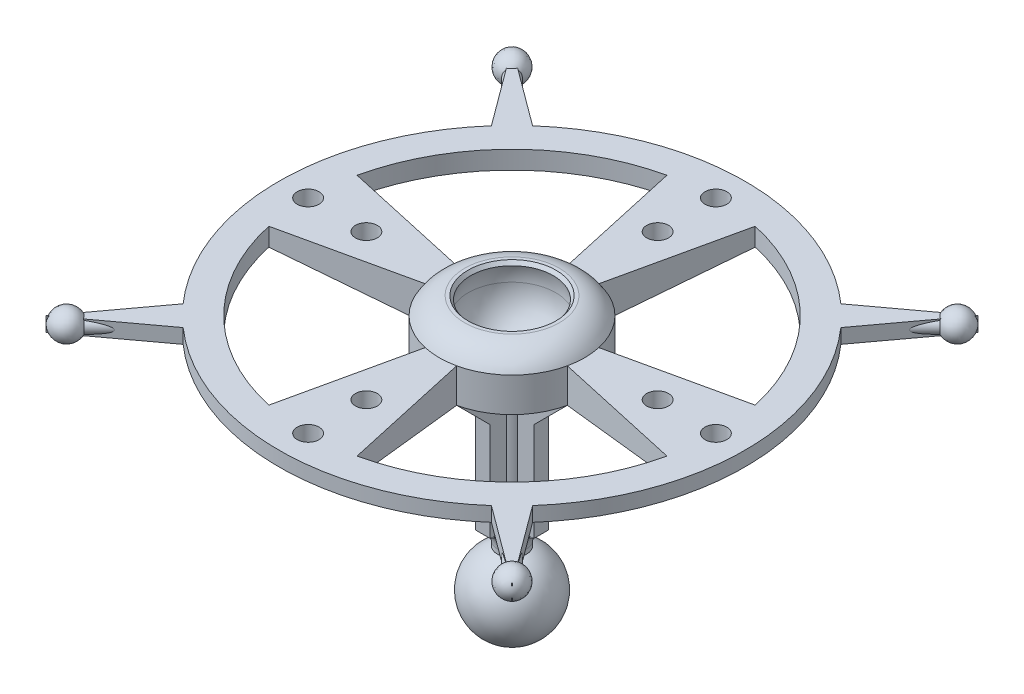
SolidWorks part; units mm, degrees
other "Markup1"
sketch "Sketch8" plane through (-15, -13.5, -15) normal (-0.6433, -0.4106, -0.6463) x (0.1908, 0.7315, -0.6546)
ref_plane "Front Plane" through (0, 0, 0) normal (0, 0, 1) x (1, 0, 0)
ref_plane "Top Plane" through (0, 0, 0) normal (0, 1, 0) x (1, 0, 0)
ref_plane "Right Plane" through (0, 0, 0) normal (1, 0, 0) x (0, 0, -1)
sketch "Sketch1" plane through (0, 0, 0) normal (1, 0, 0) x (0, 0, -1)
  line L0 (0, 4) -> (0, 0) construction
  line L1 (0, 0) -> (0, -9.5)
  line L2 (0, -9.5) -> (0, -12.3) construction
  line L3 (-4, 4) -> (-16, 4)
  line L4 (-16, 4) -> (-16, 3)
  line L5 (-16, 3) -> (-3.048, 1.4097)
  line L6 (-4, 4) -> (-3, 4)
  line L7 (0, 0.127) -> (-1, 0.127) construction
  line L8 (1, 0.127) -> (1, -9.6847) construction
  line L9 (0, -9.6847) -> (-1, -9.6847) construction
  line L10 (-1, 0.127) -> (-1, -9.6847)
  line L11 (0, -15.1) -> (0, -9.5)
  line L12 (0, 1) -> (0, 0)
  line L13 (1, 0.127) -> (0, 0.127) construction
  line L14 (1, -9.6847) -> (0, -9.6847) construction
  line L15 (0, 10.6343) -> (0, 14.716) construction
  arc A0 (-1, -9.6847) -> (0, -15.1) centre (0, -12.3) ccw
  arc A1 (-3.048, 1.4097) -> (-1, 0.127) centre (0, 4) ccw
  arc A2 (-3, 4) -> (0, 1) centre (0, 4) ccw
  arc A3 (0, 0) -> (1, 0.127) centre (0, 4) ccw construction
  arc A4 (0, 1) -> (-3, 4) centre (0, 4) ccw construction
  circle A5 centre (0, 4) radius 3 construction
  arc A6 (1, 0.127) -> (-4, 4) centre (0, 4) ccw construction
  circle A7 centre (0, 4) radius 4 construction
  arc A8 (-1, 0.127) -> (0, 0) centre (0, 4) ccw construction
  arc A9 (0, -15.1) -> (1, -9.6847) centre (0, -12.3) ccw construction
  arc A10 (1, -9.6847) -> (0, -9.5) centre (0, -12.3) ccw construction
  arc A11 (-4, 4) -> (-3.048, 1.4097) centre (0, 4) ccw construction
  arc A12 (0, -9.5) -> (-1, -9.6847) centre (0, -12.3) ccw construction
  point P11 (3.8252, 5.1695)
  point P18 (0, -12.3)
  point P20 (3.5, 4)
  dimension "D1" = 9.5
  dimension "D2" = 4
  dimension "D3" = 2.8
  dimension "D5" = 12
  dimension "D6" = 1
  dimension "D7" = 97
  dimension "D8" = 2
  dimension "D4" = 1
revolve "Revolve1" add sketch "Sketch1" angle 360 about L15 region at (0, -4.75, 0.2492)
sketch "Sketch2" plane through (0, 4, 0) normal (0, 1, 0) x (1, 0, 0)
  line L0 (-16, 0) -> (16, 0) construction
  line L1 (0.014, 16) -> (0.014, -16) construction
  circle A0 centre (0, 0) radius 0.5
  circle A1 centre (-9.5, 0) radius 0.75
  circle A2 centre (1.014, -5.5) radius 0.75
  circle A3 centre (0.014, -9.5) radius 0.75
  circle A4 centre (0.014, 9.5) radius 0.75
  circle A5 centre (9.528, 0) radius 0.75
  circle A6 centre (-5.4855, 1) radius 0.75
  circle A7 centre (-5.4855, -1) radius 0.75
  circle A8 centre (-0.986, -5.5) radius 0.75
  circle A9 centre (5.5135, -1) radius 0.75
  circle A10 centre (5.5135, 1) radius 0.75
  circle A11 centre (1.014, 5.5) radius 0.75
  circle A12 centre (-0.986, 5.5) radius 0.75
  circle A13 centre (0, 0) radius 16 construction
  dimension "D1" = 1
  dimension "D3" = 1.5
  dimension "D6" = 1.5
  dimension "D9" = 1.5
  dimension "D2" = 9.5
  dimension "D4" = 5.5
  dimension "D5" = 9.5
  dimension "D7" = 1
  dimension "D8" = 5.4995
  dimension "D10" = 1
extrude "Cut-Extrude1" [suppressed] cut sketch "Sketch2" against normal blind 30 contours A7 | A1 | A3 | A8 | A2 | A9 | A10 | A5 | A11 | A12 | A4 | A6
sketch "Sketch4" plane through (0, 4, 0) normal (0, 1, 0) x (1, 0, 0)
  line L0 (-14, 0) -> (14, 0) construction
  line L1 (-12.1489, 10.4117) -> (12.1489, 10.4117) construction
  line L2 (-12.1489, 10.4117) -> (-12.1489, -10.4117) construction
  line L3 (-12.1489, -10.4117) -> (12.1489, -10.4117) construction
  line L4 (12.1489, 10.4117) -> (12.1489, -10.4117) construction
  line L5 (0, -10.4117) -> (0, 10.4117) construction
  line L6 (-12.1489, 0) -> (12.1489, 0) construction
  line L7 (0, 13) -> (0, -14) construction
  line L8 (-1.0822, 4.8815) -> (0, 0) construction
  line L9 (1.0822, 4.8815) -> (0, 0) construction
  line L10 (-1.0822, -4.8815) -> (0, 0) construction
  line L11 (1.0822, -4.8815) -> (0, 0) construction
  line L12 (-3.463, 15.6207) -> (-1.0822, 4.8815)
  line L13 (3.463, 15.6207) -> (1.0822, 4.8815)
  line L14 (3.463, -15.6207) -> (1.0822, -4.8815)
  line L15 (-3.463, -15.6207) -> (-1.0822, -4.8815)
  line L16 (4.8815, 1.0822) -> (0, 0) construction
  line L17 (4.8815, -1.0822) -> (0, 0) construction
  line L18 (-4.8815, -1.0822) -> (0, 0) construction
  line L19 (-4.8815, 1.0822) -> (0, 0) construction
  line L20 (4.8815, 1.0822) -> (15.6207, 3.463)
  line L21 (4.8815, -1.0822) -> (15.6207, -3.463)
  line L22 (-4.8815, -1.0822) -> (-15.6207, -3.463)
  line L23 (-4.8815, 1.0822) -> (-15.6207, 3.463)
  circle A0 centre (0, 0) radius 16 construction
  circle A3 centre (0, 0) radius 5
  circle A4 centre (0, 0) radius 3
  circle A5 centre (0, 0) radius 6 construction
  circle A6 centre (0, 0) radius 3 construction
  circle A7 centre (14, 0) radius 0.75
  circle A8 centre (10, 0) radius 0.75
  circle A9 centre (0, 10) radius 0.75
  circle A10 centre (0, 14) radius 0.75
  circle A11 centre (0, -14) radius 0.75
  circle A12 centre (0, -10) radius 0.75
  circle A13 centre (-14, 0) radius 0.75
  circle A14 centre (-10, 0) radius 0.75
  circle A15 centre (0, 0) radius 16
  circle A16 centre (0, 0) radius 14
  point P0 (0, 0)
  point P59 (5.8578, 1.2986)
  dimension "D4" = 12
  dimension "D7" = 1.5
  dimension "D5" = 2
  dimension "D6" = 2
  dimension "D8" = 1.5
  dimension "D9" = 1.5
  dimension "D10" = 1.5
  dimension "D12" = 10
  dimension "D2" = 12.5
  dimension "D3" = 12.5
  dimension "D11" = 14
  dimension "D13" = 10
  dimension "D14" = 14
extrude "Cut-Extrude2" cut sketch "Sketch4" against normal blind 4 contours A3 L12 A16 L23 | A3 L22 A16 L15 | A3 L14 A16 L21 | A3 L20 A16 L13 | A13 | A14 | A9 | A10 | A12 | A11 | A8 | A7 region at (-6.8389, 4, -6.8389) region at (6.8389, 4, -6.8389) region at (-6.8389, 4, 6.8389) region at (6.8389, 4, 6.8389)
sketch "Sketch3" plane through (0, 0, 0) normal (0, 1, 0) x (1, 0, 0)
  line L1 (-0.5, 2) -> (0.5, 2)
  line L2 (-0.5, 2) -> (-0.5, -2)
  line L3 (-0.5, -2) -> (0.5, -2)
  line L4 (0.5, 2) -> (0.5, -2)
  line L5 (0, -2) -> (0, 2) construction
  line L6 (-0.5, 0) -> (0.5, 0) construction
  line L7 (-2, 0.5) -> (2, 0.5)
  line L8 (-2, 0.5) -> (-2, -0.5)
  line L9 (-2, -0.5) -> (2, -0.5)
  line L10 (2, 0.5) -> (2, -0.5)
  line L11 (0, -0.5) -> (0, 0.5) construction
  line L12 (-2, 0) -> (2, 0) construction
  point P0 (0, 0)
  point P6 (0, 0)
  dimension "D1" = 1
  dimension "D2" = 4
  dimension "D3" = 1
  dimension "D4" = 4
extrude "Boss-Extrude1" add sketch "Sketch3" against normal blind 8 and the other way up to surface contours L4 L3 L2 L1 | L9 L10 L7 L8 other way up to face at (0, 4, -3)
sketch "Sketch6" plane through (0, 0, 0) normal (0, 0, 1) x (1, 0, 0)
  line L0 (-4.8815, 1.6494) -> (-2, -1.2321)
  line L1 (-4.8815, 1.6494) -> (4.8815, 1.6494)
  line L2 (-2, 0.5722) -> (-2, -8) construction
  line L3 (0, 1.6494) -> (0, -0.8653) construction
  line L4 (4.8815, 1.6494) -> (2, -1.2321)
  line L5 (-2, -1.2321) -> (2, -1.2321)
  point P5 (0, 1.6494)
  dimension "D1" = 45
extrude "Boss-Extrude3" add sketch "Sketch6" along normal mid plane 1
sketch "Sketch5" plane through (0, 4, 0) normal (0, 1, 0) x (1, 0, 0)
  line L0 (-9.5626, 9.5626) -> (9.5626, -9.5626) construction
  line L1 (11.3137, 11.3137) -> (-11.3137, 11.3137) construction
  line L2 (11.3137, 11.3137) -> (11.3137, -11.3137) construction
  line L3 (11.3137, -11.3137) -> (-11.3137, -11.3137) construction
  line L4 (-11.3137, 11.3137) -> (-11.3137, -11.3137) construction
  line L5 (0, -11.3137) -> (0, 11.3137) construction
  line L6 (11.3137, 0) -> (-11.3137, 0) construction
  line L7 (13.6328, 13.6328) -> (-13.6328, -13.6328) construction
  line L8 (-10.5845, 11.9987) -> (-11.9987, 10.5845)
  line L9 (16, 16) -> (11.9987, 10.5845)
  line L10 (10.5845, 11.9987) -> (16, 16)
  line L11 (10.5845, 11.9987) -> (11.9987, 10.5845)
  line L12 (-28.261, -16) -> (27.3338, -16) construction
  line L13 (-25.98, 16) -> (25.98, 16) construction
  line L14 (-13.6328, 13.6328) -> (13.6328, -13.6328) construction
  line L15 (-16, 16) -> (-11.9987, 10.5845)
  line L16 (-10.5845, 11.9987) -> (-16, 16)
  line L17 (-10.5845, 11.9987) -> (-11.9987, 10.5845)
  line L18 (-9.5626, -9.5626) -> (9.5626, 9.5626) construction
  line L19 (-10.5845, -11.9987) -> (-16, -16)
  line L20 (-16, -16) -> (-11.9987, -10.5845)
  line L21 (-10.5845, -11.9987) -> (-11.9987, -10.5845)
  line L22 (10.5845, -11.9987) -> (16, -16)
  line L23 (16, -16) -> (11.9987, -10.5845)
  line L24 (10.5845, -11.9987) -> (11.9987, -10.5845)
  circle A0 centre (0, 0) radius 16 construction
  circle A1 centre (0, 0) radius 16 construction
  point P2 (0, 0)
  point P6 (0, 0)
  point P11 (0, 0)
  point P16 (0, 16)
  point P29 (-11.2916, 11.2916)
  circle M19 centre (0, 0) radius 16
  dimension "D1" = 32
  dimension "D2" = 45
  dimension "D3" = 2
extrude "Boss-Extrude2" add sketch "Sketch5" against normal blind 1 contours L16 L15 M19 | L10 L9 M19 | L22 L23 M19 | L20 L19 M19 region at (-12.8709, 4, -12.8709) region at (12.8709, 4, -12.8709) region at (-12.8709, 4, 12.8709) region at (12.8709, 4, 12.8709)
pattern_circular "CirPattern1" count 2 every 90 about axis through (0, 4, 0) along (0, -1, 0) of "Boss-Extrude3"
sketch "Sketch7" plane through (0, 0, 0) normal (1, 0, 0) x (0, 0, -1)
  line L0 (0, 3.873) -> (0, -0.127) construction
  line L1 (0, -0.127) -> (0, -8.627) construction
  line L2 (0, -8.627) -> (0, -11.127) construction
  line L3 (-4, 3.873) -> (-15, 3.873) construction
  line L4 (-15, 3.873) -> (-15, 2.873) construction
  line L5 (-15, 2.873) -> (-3.1588, 1.4191) construction
  line L6 (-4, 3.873) -> (-3, 3.873) construction
  line L7 (0, 0) -> (1, 0) construction
  line L8 (-1, 0) -> (-1, -8.8357) construction
  line L9 (0, -8.8357) -> (1, -8.8357) construction
  line L10 (1, 0) -> (1, -8.8357) construction
  line L11 (0, -13.627) -> (0, -8.627) construction
  line L12 (0, 0.873) -> (0, -0.127) construction
  line L13 (-1, 0) -> (0, 0) construction
  line L14 (-1, -8.8357) -> (0, -8.8357) construction
  line L15 (0, 10.0263) -> (0, 14.108) construction
  line L16 (-3, 3.873) -> (0, 3.873)
  line L17 (0, 3.873) -> (0, 0.873)
  arc A0 (1, -8.8357) -> (0, -13.627) centre (0, -11.127) ccw construction
  arc A1 (-3.1588, 1.4191) -> (1, 0) centre (0, 3.873) ccw
  arc A2 (-3, 3.873) -> (0, 0.873) centre (0, 3.873) ccw
  arc A3 (0, -0.127) -> (-1, 0) centre (0, 3.873) ccw construction
  arc A4 (0, 0.873) -> (-3, 3.873) centre (0, 3.873) ccw construction
  arc A5 (-1, 0) -> (-4, 3.873) centre (0, 3.873) ccw construction
  arc A6 (1, 0) -> (0, -0.127) centre (0, 3.873) ccw construction
  arc A7 (0, -13.627) -> (-1, -8.8357) centre (0, -11.127) ccw construction
  arc A8 (-1, -8.8357) -> (0, -8.627) centre (0, -11.127) ccw construction
  arc A9 (-4, 3.873) -> (-3.1588, 1.4191) centre (0, 3.873) ccw construction
  arc A10 (0, -8.627) -> (1, -8.8357) centre (0, -11.127) ccw construction
  point P14 (0, -11.127)
  dimension "D1" = 8.5
  dimension "D2" = 4
  dimension "D3" = 2.5
  dimension "D4" = 11
  dimension "D5" = 1
  dimension "D6" = 97
  dimension "D7" = 2
revolve "Cut-Revolve2" cut sketch "Sketch7" angle 360 about L15 region at (0, 2.5997, 1.2732)
ref_plane "Plane1" through (0, 3.5, 0) normal (0, 1, 0) x (1, 0, 0)
sketch "Sketch9" plane through (0, 3.5, 0) normal (0, 1, 0) x (1, 0, 0)
  line L0 (10.5845, 11.9987) -> (11.9987, 10.5845) construction
  line L1 (11.2916, 11.2916) -> (16, 16)
  line L2 (11.6451, 10.938) -> (15.043, 14.3359)
  line L3 (11.2916, 11.2916) -> (11.6451, 10.938)
  line L4 (16.9164, 16.9164) -> (17.3042, 17.3042) construction
  line L9 (0, 17.5055) -> (0, -17.5055) construction
  line L10 (-7.7081, 0) -> (7.7081, 0) construction
  line L11 (16.9164, -16.9164) -> (17.3042, -17.3042) construction
  line L15 (10.5845, -11.9987) -> (11.9987, -10.5845) construction
  line L19 (11.2916, -11.2916) -> (11.6451, -10.938)
  line L23 (11.6451, -10.938) -> (15.043, -14.3359)
  line L24 (11.2916, -11.2916) -> (16, -16)
  line L25 (-10.5845, -11.9987) -> (-11.9987, -10.5845) construction
  line L26 (-16.9164, -16.9164) -> (-17.3042, -17.3042) construction
  line L27 (-16.9164, 16.9164) -> (-17.3042, 17.3042) construction
  line L28 (-10.5845, 11.9987) -> (-11.9987, 10.5845) construction
  line L29 (-11.2916, -11.2916) -> (-16, -16)
  line L30 (-11.6451, -10.938) -> (-15.043, -14.3359)
  line L31 (-11.2916, -11.2916) -> (-11.6451, -10.938)
  line L32 (-11.2916, 11.2916) -> (-11.6451, 10.938)
  line L33 (-11.6451, 10.938) -> (-15.043, 14.3359)
  line L34 (-11.2916, 11.2916) -> (-16, 16)
  arc A2 (15.043, 14.3359) -> (16, 16) centre (15.2782, 15.3079) ccw
  arc A4 (15.043, -14.3359) -> (16, -16) centre (15.2782, -15.3079) cw
  arc A5 (-15.043, -14.3359) -> (-16, -16) centre (-15.2782, -15.3079) ccw
  arc A7 (-15.043, 14.3359) -> (-16, 16) centre (-15.2782, 15.3079) cw
  point P11 (11.2916, 11.2916)
  point P22 (0, 0)
  point P29 (0, 0)
  dimension "D2" = 1
  dimension "D3" = 1
  dimension "D1" = 0.5
revolve "Revolve2" add sketch "Sketch9" angle 360 about L4
revolve "Revolve3" add sketch "Sketch9<6>" angle 360 about L27
sketch "Sketch9<6>" plane through (0, 3.5, 0) normal (0, 1, 0) x (1, 0, 0) same geometry as "Sketch9"
revolve "Revolve4" add sketch "Sketch9<8>" angle 360 about L26
sketch "Sketch9<8>" plane through (0, 3.5, 0) normal (0, 1, 0) x (1, 0, 0) same geometry as "Sketch9"
revolve "Revolve5" add sketch "Sketch9<9>" angle 360 about L11
sketch "Sketch9<9>" plane through (0, 3.5, 0) normal (0, 1, 0) x (1, 0, 0) same geometry as "Sketch9"
sketch "Sketch10" plane through (0, 4, 0) normal (0, 1, 0) x (1, 0, 0)
  line L0 (-1.0822, 4.8815) -> (1.0822, 4.8815) construction
  line L1 (-1.0822, -4.8815) -> (1.0822, -4.8815) construction
  line L2 (0, -4.8815) -> (0, 4.8815) construction
  point P10 (0, 0)
  point P13 (0, 0)
sketch "Sketch11" plane through (0, 0, 0) normal (1, 0, 0) x (0, 0, -1)
  line L0 (-2.75, 5.199) -> (-3.25, 5.199)
  line L1 (-2.75, 5.199) -> (-2.75, 8.1758) construction
  line L2 (-4.8815, 4) -> (4.8815, 4) construction
  line L3 (0, 3.6803) -> (0, 4.3197) construction
  line L4 (-2.75, 4) -> (-2.75, 5.199) construction
  line L5 (2.75, 5.199) -> (2.75, 8.1758) construction
  line L6 (-3, 4) -> (3, 4) construction
  line L7 (-5, 4) -> (-3, 4)
  line L8 (3, 4) -> (5, 4) construction
  line L9 (-5, 4) -> (-5, 4.5) construction
  line L10 (-5, 4) -> (-4.25, 4) construction
  line L11 (-4.25, 4) -> (-4.25, 4.5) construction
  line L12 (-4.25, 4.5) -> (-5, 4.5) construction
  line L13 (-4.25, 4) -> (-5, 4) construction
  arc A0 (-2.75, 5.199) -> (-3, 4) centre (0, 4) ccw
  arc A1 (-4.9749, 4.5) -> (-5, 4) centre (0, 4) ccw
  arc A2 (5, 4) -> (2.75, 8.1758) centre (0, 4) ccw construction
  arc A3 (2.75, 8.1758) -> (-2.75, 8.1758) centre (0, 4) ccw construction
  circle A4 centre (0, 4) radius 5 construction
  arc A5 (2.75, 5.199) -> (-2.75, 5.199) centre (0, 4) ccw construction
  circle A6 centre (0, 4) radius 3 construction
  arc A7 (-5, 4) -> (5, 4) centre (0, 4) ccw construction
  arc A8 (3, 4) -> (2.75, 5.199) centre (0, 4) ccw construction
  arc A9 (-3, 4) -> (3, 4) centre (0, 4) ccw construction
  arc A10 (-3.25, 5.199) -> (-5, 4) centre (-2.9059, 2.82) ccw
  arc A11 (-2.75, 8.1758) -> (-4.9749, 4.5) centre (0, 4) ccw construction
  point P5 (2.9167, 4.8917)
  point P11 (0, 4)
  point P16 (4.05, 4)
  point P26 (-4.625, 4.5)
  dimension "D1" = 6
  dimension "D2" = 2
  dimension "D5" = 0.5
  dimension "D6" = 0.75
  dimension "D3" = 2.75
  dimension "D4" = 0.5
revolve "Revolve6" add sketch "Sketch11" angle 360 about L3 region at (0, 4.5155, 3.7339)
chamfer "Chamfer1" distance 0.25 angle 60 1 edges at (0, 5.199, -2.75) first distance on face at (0, 3.873, 2.9973)
sketch "Sketch12" plane through (0, 0, 0) normal (1, 0, 0) x (0, 0, -1)
  line L3 (-2.8, -12.3) -> (2.8, -12.3) construction
  line L4 (0, -12.3) -> (0, -1.8178) construction
  line L6 (2, -1.2321) -> (2, -8) construction
  line L7 (0.866, -8) -> (0.866, 0.127) construction
  line L10 (0.6247, -10.0752) -> (0.6177, -8.8454)
  line L11 (0.6177, -8.8454) -> (2, -8.7461)
  line L12 (2, -8.7461) -> (2, -11.3404)
  arc A2 (-1, -9.6847) -> (1, -9.6847) centre (0, -12.3) ccw construction
  arc A3 (2, -10.3404) -> (0.866, -9.6373) centre (0, -12.3) ccw construction
  arc A4 (2.8, -12.3) -> (2, -10.3404) centre (0, -12.3) ccw construction
  arc A5 (-2.8, -12.3) -> (2.8, -12.3) centre (0, -12.3) ccw construction
  arc A6 (0, -9.5) -> (-2.8, -12.3) centre (0, -12.3) ccw construction
  arc A7 (0.866, -9.6373) -> (0, -9.5) centre (0, -12.3) ccw construction
  arc A8 (2, -11.3404) -> (0.6247, -10.0752) centre (-0.2576, -12.4143) ccw
  dimension "D1" = 0.5
  dimension "D2" = 1
sketch "Sketch13" plane through (0, 0, 0) normal (1, 0, 0) x (0, 0, -1)
  line L0 (1, -9.6847) -> (1, -8) construction
  line L1 (1, -9.6847) -> (1, -8)
  line L2 (1, -8) -> (2, -8)
  line L3 (0, -10.7386) -> (0, -12.3) construction
  line L4 (0, -12.3) -> (0, -1.8178) construction
  arc A0 (2, -8) -> (1, -9.6847) centre (2.6563, -9.5287) ccw
revolve "Revolve7" add sketch "Sketch13" angle 360 about L3 region at (0, -8.3465, -1.2752)
chamfer "Chamfer2" distance 0.25 angle 45 4 edges at (-1.4142, -8, 1.4142) (1.4142, -8, 1.4142) (-1.4142, -8, -1.4142) (1.4142, -8, -1.4142) first distance on face at (0, -9.3727, 1)
sketch "Sketch14" plane through (0, 4, 0) normal (0, 1, 0) x (1, 0, 0)
  line L0 (14.2324, 14.9395) -> (14.9395, 14.2324)
  line L1 (14.9395, 14.2324) -> (13.1718, 12.4647)
  line L2 (13.1718, 12.4647) -> (12.4647, 13.1718)
  line L3 (12.4647, 13.1718) -> (14.2324, 14.9395)
  line L4 (11.2916, 11.2916) -> (16, 16) construction
  line L6 (13.449, 13.449) -> (11.9584, 13.019)
  line L7 (11.9584, 13.019) -> (13.019, 11.9584)
  line L8 (13.019, 11.9584) -> (13.449, 13.449)
  circle A0 centre (15.2782, 15.3079) radius 1
  point P10 (14.5859, 14.5859)
  dimension "D1" = 2
  dimension "D2" = 1
  dimension "D3" = 1.5
equation "\"D1@Sketch1\"=16-6.5"
